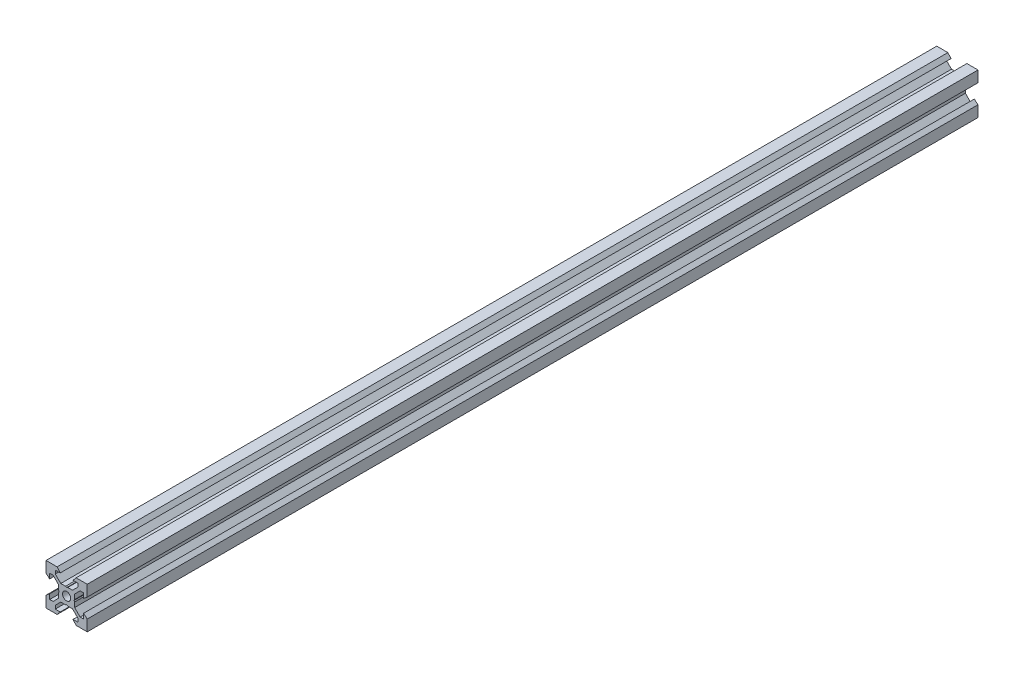
SolidWorks part; units mm, degrees
ref_plane "Front Plane" through (0, 0, 0) normal (0, 0, 1) x (1, 0, 0)
ref_plane "Top Plane" through (0, 0, 0) normal (0, 1, 0) x (1, 0, 0)
ref_plane "Right Plane" through (0, 0, 0) normal (1, 0, 0) x (0, 0, -1)
sketch "Sketch1" plane through (0, 0, 0) normal (0, 0, 1) x (1, 0, 0)
  line L0 (10, 10) -> (4.6104, 10) construction
  line L1 (10, 10) -> (10, 4.6104) construction
  line L2 (10, -10) -> (10, -4.6104) construction
  line L3 (10, -10) -> (4.6104, -10) construction
  line L4 (10, 10) -> (10, 4.6104)
  line L5 (6.5607, 5.5) -> (8.2, 5.5)
  line L6 (5.5, 8.2) -> (5.5, 6.5607)
  line L7 (10, 10) -> (4.6104, 10)
  line L8 (10, 10) -> (10, 4.6104)
  line L9 (6.5607, 5.5) -> (3.9, 2.8393)
  line L10 (5.5, 6.5607) -> (2.8393, 3.9)
  line L11 (10, 4.6104) -> (8.2, 3.1)
  line L12 (4.6104, 10) -> (3.1, 8.2)
  line L13 (8.2, 3.1) -> (8.2, 5.5)
  line L14 (3.1, 8.2) -> (5.5, 8.2)
  line L15 (-6.5607, 5.5) -> (-8.2, 5.5)
  line L16 (6.5607, -5.5) -> (8.2, -5.5)
  line L17 (3.1, -8.2) -> (5.5, -8.2)
  line L18 (8.2, -3.1) -> (8.2, -5.5)
  line L19 (4.6104, -10) -> (3.1, -8.2)
  line L20 (10, -4.6104) -> (8.2, -3.1)
  line L21 (0.5196, -3.9) -> (0, -3.6)
  line L22 (0.5196, 3.9) -> (0, 3.6)
  line L23 (3.6, 0) -> (3.9, -0.5196)
  line L24 (3.9, 0.5196) -> (3.6, 0)
  line L25 (3.9, 0.5196) -> (3.9, 2.8393)
  line L26 (2.8393, 3.9) -> (0.5196, 3.9)
  line L27 (3.9, -2.8393) -> (3.9, -0.5196)
  line L28 (2.8393, -3.9) -> (0.5196, -3.9)
  line L29 (5.5, -6.5607) -> (2.8393, -3.9)
  line L30 (6.5607, -5.5) -> (3.9, -2.8393)
  line L31 (10, -10) -> (10, -4.6104)
  line L32 (10, -10) -> (4.6104, -10)
  line L33 (5.5, -8.2) -> (5.5, -6.5607)
  line L34 (-6.5607, -5.5) -> (-8.2, -5.5)
  line L35 (10, -10) -> (10, -4.6104)
  line L36 (0, 0) -> (0, 8.2) construction
  line L37 (-10, -10) -> (-4.6104, -10) construction
  line L38 (-10, -10) -> (-10, -4.6104) construction
  line L39 (-10, 10) -> (-10, 4.6104) construction
  line L40 (-10, 10) -> (-4.6104, 10) construction
  line L41 (-10, -10) -> (-10, -4.6104)
  line L43 (-5.5, -8.2) -> (-5.5, -6.5607)
  line L44 (-10, -10) -> (-4.6104, -10)
  line L45 (-10, -10) -> (-10, -4.6104)
  line L46 (-6.5607, -5.5) -> (-3.9, -2.8393)
  line L47 (-5.5, -6.5607) -> (-2.8393, -3.9)
  line L48 (-2.8393, -3.9) -> (-0.5196, -3.9)
  line L49 (-3.9, -2.8393) -> (-3.9, -0.5196)
  line L50 (-2.8393, 3.9) -> (-0.5196, 3.9)
  line L51 (-3.9, 0.5196) -> (-3.9, 2.8393)
  line L52 (-3.9, 0.5196) -> (-3.6, 0)
  line L53 (-3.6, 0) -> (-3.9, -0.5196)
  line L54 (-0.5196, 3.9) -> (0, 3.6)
  line L55 (-0.5196, -3.9) -> (0, -3.6)
  line L56 (-10, -4.6104) -> (-8.2, -3.1)
  line L57 (-4.6104, -10) -> (-3.1, -8.2)
  line L58 (-8.2, -3.1) -> (-8.2, -5.5)
  line L59 (-3.1, -8.2) -> (-5.5, -8.2)
  line L60 (-10, -10) -> (10, -10) construction
  line L61 (-10, -10) -> (-10, 10) construction
  line L62 (-3.1, 8.2) -> (-5.5, 8.2)
  line L63 (-8.2, 3.1) -> (-8.2, 5.5)
  line L64 (-4.6104, 10) -> (-3.1, 8.2)
  line L65 (-10, 4.6104) -> (-8.2, 3.1)
  line L66 (-5.5, 6.5607) -> (-2.8393, 3.9)
  line L67 (-6.5607, 5.5) -> (-3.9, 2.8393)
  line L68 (-10, 10) -> (-10, 4.6104)
  line L69 (-10, 10) -> (-4.6104, 10)
  line L70 (-5.5, 8.2) -> (-5.5, 6.5607)
  line L71 (-10, 10) -> (10, 10) construction
  line L72 (-10, 10) -> (-10, 4.6104)
  line L73 (10, -10) -> (10, 10) construction
  line L74 (-10, -10) -> (10, 10) construction
  line L75 (-10, 10) -> (10, -10) construction
  circle A0 centre (0, 0) radius 2
  dimension "D7" = 4
  dimension "D1" = 20
  dimension "D2" = 5.3896
  dimension "D3" = 4.5
  dimension "D4" = 50
  dimension "D5" = 1.8
  dimension "D6" = 1.5104
  dimension "D8" = 5.5
  dimension "D9" = 120
  dimension "D10" = 0.3
  dimension "D11" = 2.3197
  dimension "D12" = 7.8
  dimension "D13" = 7.8
  dimension "D14" = 1.5
  dimension "D15" = 2.6607
extrude "Boss-Extrude1" add sketch "Sketch1" along normal mid plane 432 contours L70 L62 L64 L69 L68 L65 L63 L15 L67 L51 L52 L53 L49 L46 L34 L58 L56 L41 L44 L57 L59 L43 L47 L48 L55 L21 L28 L29 L33 L17 L19 L32 L31 L20 L18 L16 L30 L27 L23 L24 L25 L9 L5 L13 L11 L4 L7 L12 L14 L6 L10 region at (9.7172, 7.3052, 0)
